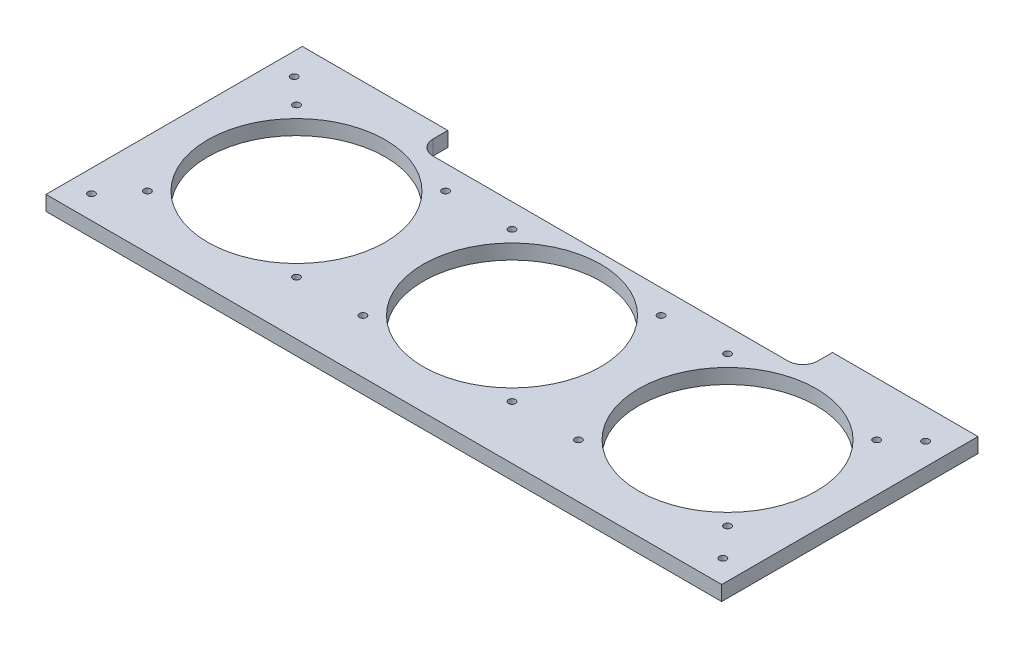
SolidWorks part; units mm, degrees
ref_plane "Front Plane" through (0, 0, 0) normal (0, 0, 1) x (1, 0, 0)
ref_plane "Top Plane" through (0, 0, 0) normal (0, 1, 0) x (1, 0, 0)
ref_plane "Right Plane" through (0, 0, 0) normal (1, 0, 0) x (0, 0, -1)
sketch "Sketch1" plane through (0, 0, 0) normal (0, 1, 0) x (1, 0, 0)
  line L0 (0, 0) -> (145, 55) construction
  line L1 (0, 0) -> (145, 0)
  line L2 (0, 0) -> (0, 55)
  line L3 (0, 55) -> (145, 55)
  line L4 (145, 0) -> (145, 55)
  point P5 (72.5, 27.5)
  dimension "D1" = 145
  dimension "D2" = 55
extrude "Boss-Extrude1" add sketch "Sketch1" along normal blind 3.175
ref_plane "Plane1" through (72.5, 0, 0) normal (1, 0, 0) x (0, 0, -1)
ref_plane "Plane2" through (0, 0, -27.5) normal (0, 0, -1) x (-1, 0, 0)
sketch "Sketch3" plane through (0, 3.175, 0) normal (0, 1, 0) x (1, 0, 0)
  line L0 (0, 0) -> (145, 55) construction
  point P4 (72.5, 27.5)
ref_axis "Axis1" through (72.5, 3.175, -27.5) along (0, 1, 0)
sketch "Sketch4" plane through (0, 0, 0) normal (0, -1, 0) x (1, 0, 0)
  line L0 (6.25, -7.5) -> (6.25, -47.5) construction
  line L1 (6.25, -47.5) -> (46.25, -47.5) construction
  line L2 (46.25, -47.5) -> (46.25, -7.5) construction
  line L3 (46.25, -7.5) -> (6.25, -7.5) construction
  line L4 (52.5, -7.5) -> (52.5, -47.5) construction
  line L5 (52.5, -47.5) -> (92.5, -47.5) construction
  line L6 (92.5, -47.5) -> (92.5, -7.5) construction
  line L7 (92.5, -7.5) -> (52.5, -7.5) construction
  line L8 (98.75, -7.5) -> (98.75, -47.5) construction
  line L9 (98.75, -47.5) -> (138.75, -47.5) construction
  line L10 (138.75, -47.5) -> (138.75, -7.5) construction
  line L11 (138.75, -7.5) -> (98.75, -7.5) construction
  line L12 (6.25, -7.5) -> (6.25, -47.5) construction
  line L13 (6.25, -47.5) -> (46.25, -47.5) construction
  line L14 (46.25, -47.5) -> (46.25, -7.5) construction
  line L15 (46.25, -7.5) -> (6.25, -7.5) construction
  line L16 (52.5, -7.5) -> (52.5, -47.5) construction
  line L17 (52.5, -47.5) -> (92.5, -47.5) construction
  line L18 (92.5, -47.5) -> (92.5, -7.5) construction
  line L19 (92.5, -7.5) -> (52.5, -7.5) construction
  line L20 (98.75, -7.5) -> (98.75, -47.5) construction
  line L21 (98.75, -47.5) -> (138.75, -47.5) construction
  line L22 (138.75, -47.5) -> (138.75, -7.5) construction
  line L23 (138.75, -7.5) -> (98.75, -7.5) construction
  line L24 (72.5, -55) -> (72.5, 0) construction
  line L25 (145, -55) -> (0, -55) construction
  line L26 (0, 0) -> (145, 0) construction
  line L27 (110.6, -3.175) -> (34.4, -3.175) construction
  line L28 (110.6, -6.35) -> (34.4, -6.35) construction
  line L29 (113.775, 0) -> (31.225, 0) construction
  line L30 (31.225, -3.175) -> (31.225, 0) construction
  line L31 (113.775, -3.175) -> (113.775, 0) construction
  line L32 (145, -27.5) -> (0, -27.5) construction
  line L33 (145, 0) -> (145, -55) construction
  line L34 (0, -55) -> (0, 0) construction
  line L35 (110.6, -51.825) -> (34.4, -51.825) construction
  line L36 (113.775, -51.825) -> (113.775, -55)
  line L37 (31.225, -51.825) -> (31.225, -55)
  line L38 (113.775, -55) -> (31.225, -55)
  line L39 (110.6, -48.65) -> (34.4, -48.65)
  circle A0 centre (10.25, -11.5) radius 0.75 construction
  circle A1 centre (10.25, -43.5) radius 0.75 construction
  circle A2 centre (42.25, -43.5) radius 0.75 construction
  circle A3 centre (26.25, -27.5) radius 19.05 construction
  circle A4 centre (42.25, -11.5) radius 0.75 construction
  circle A5 centre (56.5, -11.5) radius 0.75 construction
  circle A6 centre (56.5, -43.5) radius 0.75 construction
  circle A7 centre (88.5, -43.5) radius 0.75 construction
  circle A8 centre (88.5, -11.5) radius 0.75 construction
  circle A9 centre (72.5, -27.5) radius 19.05 construction
  circle A10 centre (102.75, -11.5) radius 0.75 construction
  circle A11 centre (102.75, -43.5) radius 0.75 construction
  circle A12 centre (134.75, -43.5) radius 0.75 construction
  circle A13 centre (134.75, -11.5) radius 0.75 construction
  circle A14 centre (118.75, -27.5) radius 19.05 construction
  circle A15 centre (10.25, -11.5) radius 0.75
  circle A16 centre (10.25, -43.5) radius 0.75
  circle A17 centre (42.25, -43.5) radius 0.75
  circle A18 centre (26.25, -27.5) radius 19.05
  circle A19 centre (42.25, -11.5) radius 0.75
  circle A20 centre (56.5, -11.5) radius 0.75
  circle A21 centre (56.5, -43.5) radius 0.75
  circle A22 centre (88.5, -43.5) radius 0.75
  circle A23 centre (88.5, -11.5) radius 0.75
  circle A24 centre (72.5, -27.5) radius 19.05
  circle A25 centre (102.75, -11.5) radius 0.75
  circle A26 centre (102.75, -43.5) radius 0.75
  circle A27 centre (134.75, -43.5) radius 0.75
  circle A28 centre (134.75, -11.5) radius 0.75
  circle A29 centre (118.75, -27.5) radius 19.05
  circle A30 centre (4.75, -5) radius 1.7 construction
  circle A31 centre (4.75, -48.5) radius 1.7 construction
  circle A32 centre (140.25, -5) radius 1.7 construction
  circle A33 centre (140.25, -48.5) radius 1.7 construction
  circle A34 centre (4.75, -5) radius 1.7 construction
  circle A35 centre (4.75, -48.5) radius 1.7 construction
  circle A36 centre (140.25, -5) radius 1.7 construction
  circle A37 centre (140.25, -48.5) radius 1.7 construction
  arc A38 (110.6, -6.35) -> (113.775, -3.175) centre (110.6, -3.175) ccw construction
  arc A39 (31.225, -3.175) -> (34.4, -6.35) centre (34.4, -3.175) ccw construction
  arc A40 (31.225, -51.825) -> (34.4, -48.65) centre (34.4, -51.825) cw
  arc A41 (110.6, -48.65) -> (113.775, -51.825) centre (110.6, -51.825) cw
  circle A42 centre (4.75, -48.5) radius 0.75
  circle A43 centre (4.75, -5) radius 0.75
  circle A44 centre (140.25, -5) radius 0.75
  circle A45 centre (140.25, -48.5) radius 0.75
  point P77 (72.5, -3.175)
  point P98 (72.5, -51.825)
  dimension "D1" = 3.175
  dimension "D4" = 1.5
  dimension "D2" = 76.2
  dimension "D3" = 3.175
extrude "Cut-Extrude1" cut sketch "Sketch4" against normal through all
